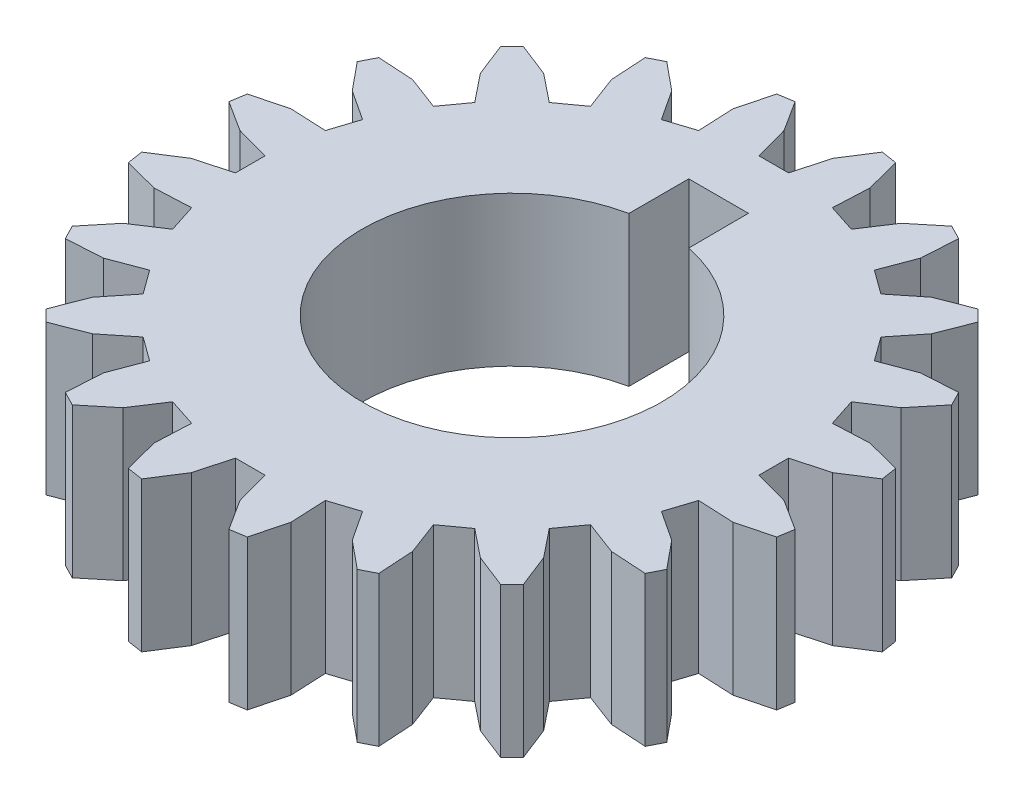
SolidWorks part; units mm, degrees
ref_plane "前视基准面" through (0, 0, 0) normal (0, 0, 1) x (1, 0, 0)
ref_plane "上视基准面" through (0, 0, 0) normal (0, 1, 0) x (1, 0, 0)
ref_plane "右视基准面" through (0, 0, 0) normal (1, 0, 0) x (0, 0, -1)
sketch "草图1" plane through (0, 0, 0) normal (0, 1, 0) x (1, 0, 0)
  line L0 (-14.6837, 10.1191) -> (-16.557, 11.6179)
  line L1 (-16.557, 11.6179) -> (-18.7904, 12.4939)
  line L2 (-18.7904, 12.4939) -> (-19.5462, 11.7381)
  line L3 (-19.5462, 11.7381) -> (-18.6702, 9.5047)
  line L4 (-18.6702, 9.5047) -> (-17.1714, 7.6314)
  line L5 (-17.1714, 7.6314) -> (-18.3307, 6.0357)
  line L6 (-13.9346, 13.5232) -> (-13.088, 11.2784)
  line L7 (-14.0776, 15.918) -> (-13.9346, 13.5232)
  line L8 (-13.1252, 16.4032) -> (-14.0776, 15.918)
  line L9 (-11.2718, 14.8799) -> (-13.1252, 16.4032)
  line L10 (-9.9534, 12.8756) -> (-11.2718, 14.8799)
  line L11 (-13.088, 11.2784) -> (-14.6837, 10.1191)
  line L12 (-8.189, 15.8816) -> (-8.0776, 13.4851)
  line L13 (-7.585, 18.2034) -> (-8.189, 15.8816)
  line L14 (-6.5293, 18.3706) -> (-7.585, 18.2034)
  line L15 (-5.2373, 16.3491) -> (-6.5293, 18.3706)
  line L16 (-4.6027, 14.0354) -> (-5.2373, 16.3491)
  line L17 (-8.0776, 13.4851) -> (-9.9534, 12.8756)
  line L18 (-1.9959, 16.3491) -> (-2.6304, 14.0354)
  line L19 (-0.7039, 18.3706) -> (-1.9959, 16.3491)
  line L20 (0.3518, 18.2034) -> (-0.7039, 18.3706)
  line L21 (0.9559, 15.8816) -> (0.3518, 18.2034)
  line L22 (0.8444, 13.4851) -> (0.9559, 15.8816)
  line L23 (-2.6304, 14.0354) -> (-4.6027, 14.0354)
  line L24 (4.0387, 14.8799) -> (2.7202, 12.8756)
  line L25 (5.8921, 16.4032) -> (4.0387, 14.8799)
  line L26 (6.8445, 15.918) -> (5.8921, 16.4032)
  line L27 (6.7015, 13.5232) -> (6.8445, 15.918)
  line L28 (5.8549, 11.2784) -> (6.7015, 13.5232)
  line L29 (2.7202, 12.8756) -> (0.8444, 13.4851)
  line L30 (9.3239, 11.6179) -> (7.4506, 10.1191)
  line L31 (11.5573, 12.4939) -> (9.3239, 11.6179)
  line L32 (12.3131, 11.7381) -> (11.5573, 12.4939)
  line L33 (11.4371, 9.5047) -> (12.3131, 11.7381)
  line L34 (9.9383, 7.6314) -> (11.4371, 9.5047)
  line L35 (7.4506, 10.1191) -> (5.8549, 11.2784)
  line L36 (13.3423, 6.8823) -> (11.0976, 6.0357)
  line L37 (15.7372, 7.0253) -> (13.3423, 6.8823)
  line L38 (16.2224, 6.0729) -> (15.7372, 7.0253)
  line L39 (14.6991, 4.2195) -> (16.2224, 6.0729)
  line L40 (12.6948, 2.9011) -> (14.6991, 4.2195)
  line L41 (11.0976, 6.0357) -> (9.9383, 7.6314)
  line L42 (15.7008, 1.1367) -> (13.3043, 1.0252)
  line L43 (18.0226, 0.5326) -> (15.7008, 1.1367)
  line L44 (18.1898, -0.523) -> (18.0226, 0.5326)
  line L45 (16.1683, -1.815) -> (18.1898, -0.523)
  line L46 (13.8546, -2.4496) -> (16.1683, -1.815)
  line L47 (13.3043, 1.0252) -> (12.6948, 2.9011)
  line L48 (16.1683, -5.0564) -> (13.8546, -4.4219)
  line L49 (18.1898, -6.3484) -> (16.1683, -5.0564)
  line L50 (18.0226, -7.4041) -> (18.1898, -6.3484)
  line L51 (15.7008, -8.0082) -> (18.0226, -7.4041)
  line L52 (13.3043, -7.8967) -> (15.7008, -8.0082)
  line L53 (13.8546, -4.4219) -> (13.8546, -2.4496)
  line L54 (14.6991, -11.091) -> (12.6948, -9.7725)
  line L55 (16.2224, -12.9444) -> (14.6991, -11.091)
  line L56 (15.7372, -13.8968) -> (16.2224, -12.9444)
  line L57 (13.3423, -13.7538) -> (15.7372, -13.8968)
  line L58 (11.0976, -12.9072) -> (13.3423, -13.7538)
  line L59 (12.6948, -9.7725) -> (13.3043, -7.8967)
  line L60 (11.4371, -16.3762) -> (9.9383, -14.5029)
  line L61 (12.3131, -18.6096) -> (11.4371, -16.3762)
  line L62 (11.5573, -19.3654) -> (12.3131, -18.6096)
  line L63 (9.3239, -18.4894) -> (11.5573, -19.3654)
  line L64 (7.4506, -16.9906) -> (9.3239, -18.4894)
  line L65 (9.9383, -14.5029) -> (11.0976, -12.9072)
  line L66 (6.7015, -20.3946) -> (5.8549, -18.1499)
  line L67 (6.8445, -22.7895) -> (6.7015, -20.3946)
  line L68 (5.8921, -23.2747) -> (6.8445, -22.7895)
  line L69 (4.0387, -21.7514) -> (5.8921, -23.2747)
  line L70 (2.7202, -19.7471) -> (4.0387, -21.7514)
  line L71 (5.8549, -18.1499) -> (7.4506, -16.9906)
  line L72 (0.9559, -22.7531) -> (0.8444, -20.3566)
  line L73 (0.3518, -25.0749) -> (0.9559, -22.7531)
  line L74 (-0.7039, -25.2421) -> (0.3518, -25.0749)
  line L75 (-1.9959, -23.2206) -> (-0.7039, -25.2421)
  line L76 (-2.6304, -20.9069) -> (-1.9959, -23.2206)
  line L77 (0.8444, -20.3566) -> (2.7202, -19.7471)
  line L78 (-5.2373, -23.2206) -> (-4.6027, -20.9069)
  line L79 (-6.5293, -25.2421) -> (-5.2373, -23.2206)
  line L80 (-7.585, -25.0749) -> (-6.5293, -25.2421)
  line L81 (-8.189, -22.7531) -> (-7.585, -25.0749)
  line L82 (-8.0776, -20.3566) -> (-8.189, -22.7531)
  line L83 (-4.6027, -20.9069) -> (-2.6304, -20.9069)
  line L84 (-11.2718, -21.7514) -> (-9.9534, -19.7471)
  line L85 (-13.1252, -23.2747) -> (-11.2718, -21.7514)
  line L86 (-14.0776, -22.7895) -> (-13.1252, -23.2747)
  line L87 (-13.9346, -20.3946) -> (-14.0776, -22.7895)
  line L88 (-13.088, -18.1499) -> (-13.9346, -20.3946)
  line L89 (-9.9534, -19.7471) -> (-8.0776, -20.3566)
  line L90 (-16.557, -18.4894) -> (-14.6837, -16.9906)
  line L91 (-18.7904, -19.3654) -> (-16.557, -18.4894)
  line L92 (-19.5462, -18.6096) -> (-18.7904, -19.3654)
  line L93 (-18.6702, -16.3762) -> (-19.5462, -18.6096)
  line L94 (-17.1714, -14.5029) -> (-18.6702, -16.3762)
  line L95 (-14.6837, -16.9906) -> (-13.088, -18.1499)
  line L96 (-20.5755, -13.7538) -> (-18.3307, -12.9072)
  line L97 (-22.9703, -13.8968) -> (-20.5755, -13.7538)
  line L98 (-23.4556, -12.9444) -> (-22.9703, -13.8968)
  line L99 (-21.9323, -11.091) -> (-23.4556, -12.9444)
  line L100 (-19.9279, -9.7725) -> (-21.9323, -11.091)
  line L101 (-18.3307, -12.9072) -> (-17.1714, -14.5029)
  line L102 (-22.9339, -8.0082) -> (-20.5374, -7.8967)
  line L103 (-25.2557, -7.4041) -> (-22.9339, -8.0082)
  line L104 (-25.4229, -6.3484) -> (-25.2557, -7.4041)
  line L105 (-23.4014, -5.0564) -> (-25.4229, -6.3484)
  line L106 (-21.0878, -4.4219) -> (-23.4014, -5.0564)
  line L107 (-20.5374, -7.8967) -> (-19.9279, -9.7725)
  line L108 (-23.4014, -1.815) -> (-21.0878, -2.4496)
  line L109 (-25.4229, -0.523) -> (-23.4014, -1.815)
  line L110 (-25.2557, 0.5326) -> (-25.4229, -0.523)
  line L111 (-22.9339, 1.1367) -> (-25.2557, 0.5326)
  line L112 (-20.5374, 1.0252) -> (-22.9339, 1.1367)
  line L113 (-21.0878, -2.4496) -> (-21.0878, -4.4219)
  line L114 (-21.9323, 4.2195) -> (-19.9279, 2.9011)
  line L115 (-23.4556, 6.0729) -> (-21.9323, 4.2195)
  line L116 (-22.9703, 7.0253) -> (-23.4556, 6.0729)
  line L117 (-20.5755, 6.8823) -> (-22.9703, 7.0253)
  line L118 (-18.3307, 6.0357) -> (-20.5755, 6.8823)
  line L119 (-19.9279, 2.9011) -> (-20.5374, 1.0252)
  line L120 (-5.6166, 6.3622) -> (-5.6166, 10.3622)
  line L121 (-5.6166, 10.3622) -> (-1.6351, 10.3622)
  line L122 (-1.6351, 10.3622) -> (-1.6166, 6.3622)
  arc A0 (-5.6166, 6.3622) -> (-1.6166, 6.3622) centre (-3.6166, -3.4357) ccw
  point P125 (-3.6166, -3.4357)
extrude "凸台-拉伸1" add sketch "草图1" along normal blind 10
